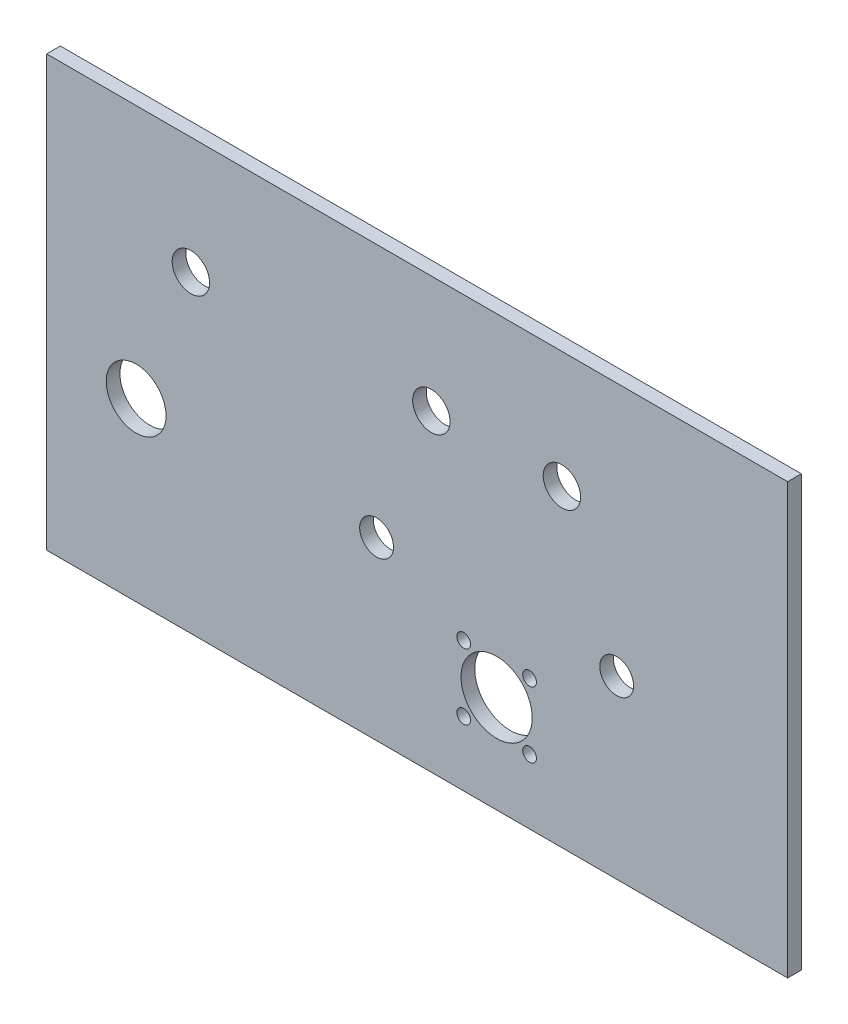
SolidWorks part; units mm, degrees
ref_plane "Спереди" through (0, 0, 0) normal (0, 0, 1) x (1, 0, 0)
ref_plane "Сверху" through (0, 0, 0) normal (0, 1, 0) x (1, 0, 0)
ref_plane "Справа" through (0, 0, 0) normal (1, 0, 0) x (0, 0, -1)
sketch "Эскиз1" plane through (0, 0, 0) normal (0, 0, 1) x (1, 0, 0)
  line L0 (-12.0208, 12.0208) -> (0, 0) construction
  line L1 (-164.3075, 121.3279) -> (106.2638, 121.3279)
  line L2 (-164.3075, 121.3279) -> (-164.3075, -35.6189)
  line L3 (-164.3075, -35.6189) -> (106.2638, -35.6189)
  line L4 (106.2638, 121.3279) -> (106.2638, -35.6189)
  line L5 (0, 0) -> (0, 121.3279) construction
  circle A0 centre (0, 0) radius 13
  circle A1 centre (-12.0208, 12.0208) radius 2.5
  circle A2 centre (12.0208, 12.0208) radius 2.5
  circle A3 centre (12.0208, -12.0208) radius 2.5
  circle A4 centre (-12.0208, -12.0208) radius 2.5
  circle A5 centre (-43.8338, 28.6526) radius 6.1833
  circle A6 centre (43.8338, 28.6526) radius 6.1833
  circle A7 centre (-131.6431, 28.6526) radius 10.922
  circle A8 centre (-23.8338, 78.6526) radius 6.8262
  circle A9 centre (23.8338, 78.6526) radius 6.8262
  circle A10 centre (-111.6431, 78.6526) radius 6.8262
  point P19 (0, 0)
  point P29 (0, 0)
  point P30 (15.8602, 102.7682)
  point P31 (-126.1418, 20.8932)
  point P32 (-111.6431, 99.1435)
  point P33 (0, 0)
  point P34 (0, 121.3279)
  point P35 (0, 0)
  point P36 (0, 0)
  point P37 (-20.6427, 86.5962)
  point P38 (43.8338, 28.6526)
  point P39 (-21.7789, 101.6502)
  dimension "D2" = 5
  dimension "D4" = 26
  dimension "D1" = 45
  dimension "D3" = 17
  dimension "D6" = 50
  dimension "D7" = 20
  dimension "D8" = 20
  dimension "D5" = 4
extrude "Бобышка-Вытянуть1" add sketch "Эскиз1" along normal blind 5
equation "\"Диаметр резьбы редуктора\" = 4  'Диаметр резьбы на фланце"
equation "\"Глубина резьбы редуктора\" = 7  'Диаметр резьбы на фланце"
equation "\"Диаметр окружности расположения редуктора\" = 34  'Диаметр расположения резьбы на фланце"
equation "\"Диаметр бурта редуктора\" = 26  'Диаметр бурта на фланце (Посадка h7)"
equation "\"Угл сдвига редуктора\" = 45"
equation "\"D1@Эскиз1\"=\"Угл сдвига редуктора\""
equation "\"D2@Эскиз1\"=\"Диаметр резьбы редуктора\"+1"
equation "\"D3@Эскиз1\"=\"Диаметр окружности расположения редуктора\"/2"
equation "\"D4@Эскиз1\"=\"Диаметр бурта редуктора\""
equation "\"Толщина пластины\" = 5"
equation "\"Межосевое прижима Вертикаль\" = 50  '!!!"
equation "\"Межосевое прижима Горизонталь\" = 20  '!!!"
equation "\"D7@Эскиз1\"=\"Межосевое прижима Горизонталь\""
equation "\"D8@Эскиз1\"=\"Межосевое прижима Горизонталь\""
equation "\"D1@Бобышка-Вытянуть1\"=\"Толщина пластины\""
equation "\"D6@Эскиз1\"=\"Межосевое прижима Вертикаль\""
